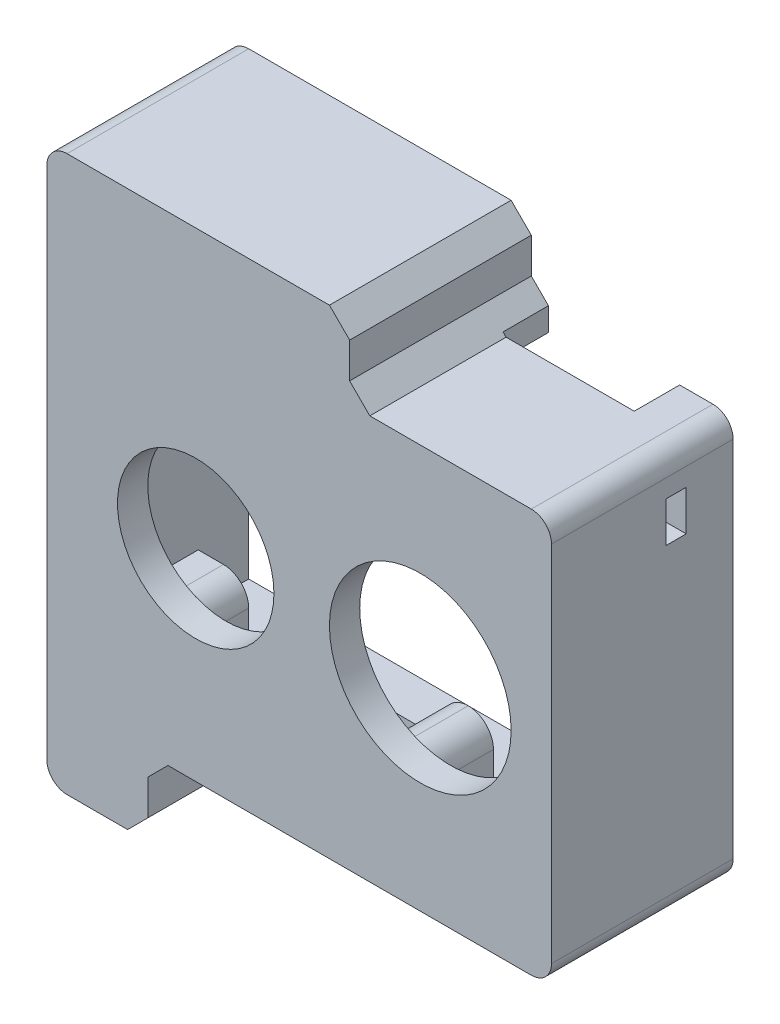
SolidWorks part; units mm, degrees
ref_plane "Front Plane" through (0, 0, 0) normal (0, 0, 1) x (1, 0, 0)
ref_plane "Top Plane" through (0, 0, 0) normal (0, 1, 0) x (1, 0, 0)
ref_plane "Right Plane" through (0, 0, 0) normal (1, 0, 0) x (0, 0, -1)
sketch "Sketch1" plane through (0, 0, 0) normal (0, 0, 1) x (1, 0, 0)
  line L0 (-15, -27.5) -> (-15, -20)
  line L1 (-25, -27.5) -> (-15, -27.5)
  line L2 (-25, -27.5) -> (-25, 27.5)
  line L3 (-25, 27.5) -> (5, 27.5)
  line L4 (25, -20) -> (25, 20)
  line L5 (0, 0) -> (25, 0) construction
  line L6 (0, 0) -> (-25, 0) construction
  line L7 (-23, -18) -> (23, -18)
  line L8 (-23, -18) -> (-23, 18)
  line L9 (-23, 18) -> (23, 18)
  line L10 (23, -18) -> (23, 18)
  line L11 (-23, -18) -> (23, 18) construction
  line L12 (-23, 18) -> (23, -18) construction
  line L13 (-15, -20) -> (25, -20)
  line L14 (5, 27.5) -> (5, 20)
  line L15 (5, 20) -> (25, 20)
  point P0 (0, 0)
  point P1 (-25, 0)
  point P4 (25, 0)
  point P6 (0, 0)
  point P18 (23, 0)
  point P20 (0, 18)
  dimension "D1" = 55
  dimension "D2" = 30
  dimension "D3" = 46
  dimension "D4" = 36
  dimension "D5" = 40
  dimension "D6" = 10
  dimension "D7" = 50
extrude "Boss-Extrude1" add sketch "Sketch1" along normal blind 15
sketch "Sketch2" plane through (0, 0, 15) normal (0, 0, 1) x (1, 0, 0)
  line L12 (-25, 27.5) -> (-25, -27.5)
  line L13 (-25, -27.5) -> (-15, -27.5)
  line L14 (-15, -27.5) -> (-15, -20)
  line L15 (-15, -20) -> (25, -20)
  line L16 (25, -20) -> (25, 20)
  line L17 (25, 20) -> (5, 20)
  line L18 (5, 20) -> (5, 27.5)
  line L19 (5, 27.5) -> (-25, 27.5)
  line L20 (-25, 27.5) -> (-25, -27.5)
  line L21 (-25, -27.5) -> (-15, -27.5)
  line L22 (-15, -27.5) -> (-15, -20)
  line L23 (-15, -20) -> (25, -20)
  line L24 (25, -20) -> (25, 20)
  line L25 (25, 20) -> (5, 20)
  line L26 (5, 20) -> (5, 27.5)
  line L27 (5, 27.5) -> (-25, 27.5)
  dimension "D1" = 0
extrude "Boss-Extrude2" add sketch "Sketch2" along normal blind 3
sketch "Sketch3" plane through (0, 0, 18) normal (0, 0, 1) x (1, 0, 0)
  circle A0 centre (-10.25, 0) radius 7.75
  circle A1 centre (12, 0) radius 9
  point P6 (0, 0)
  point P8 (0, 0)
  point P9 (0, 0)
  point P10 (0, 0)
  dimension "D1" = 18
  dimension "D2" = 15.5
  dimension "D3" = 10.25
  dimension "D4" = 12
extrude "Cut-Extrude1" cut sketch "Sketch3" against normal blind 10
sketch "Sketch4" plane through (0, 0, 15) normal (0, 0, -1) x (-1, 0, 0)
  line L0 (18, -18) -> (18, -13)
  line L1 (23, -18) -> (-23, -18) construction
  line L2 (18, -13) -> (23, -13)
  line L3 (23, 18) -> (23, -18) construction
  line L4 (23, -18) -> (23, -13)
  line L5 (23, -18) -> (18, -18)
  line L6 (-23, 18) -> (23, 18) construction
  line L7 (-1.248, -18) -> (-6.248, -18)
  line L8 (-1.248, -18) -> (-1.248, -13)
  line L9 (-1.248, -13) -> (-6.248, -13)
  line L10 (-6.248, -18) -> (-6.248, -13)
  line L11 (-1.248, 18) -> (-6.248, 18)
  line L12 (-1.248, 18) -> (-1.248, 13)
  line L13 (-1.248, 13) -> (-6.248, 13)
  line L14 (-6.248, 18) -> (-6.248, 13)
  line L16 (18, 18) -> (23, 18)
  line L17 (18, 18) -> (18, 13)
  line L18 (18, 13) -> (23, 13)
  line L19 (23, 18) -> (23, 13)
  circle A0 centre (20.252, -15.1962) radius 1
  circle A1 centre (-3.748, -15.1962) radius 1
  circle A2 centre (-3.748, 15.2038) radius 1
  circle A3 centre (20.252, 15.2038) radius 1
  point P32 (0, 0)
  point P33 (0, 0)
  point P34 (0, 0)
  point P35 (0, 0)
  point P36 (-3.748, -18)
  point P37 (0, 0)
  dimension "D1" = 2
  dimension "D2" = 5
  dimension "D4" = 24
  dimension "D5" = 30.4
extrude "Boss-Extrude3" add sketch "Sketch4" along normal blind 10
fillet "Fillet1" radius 2.5 6 edges at (6.248, -13, 10) (1.248, -13, 10) (-18, -13, 10) (-18, 13, 10) (1.248, 13, 10) (6.248, 13, 10)
sketch "Sketch6" plane through (0, 0, -3) normal (0, 0, -1) x (-1, 0, 0)
  line L0 (20, 22.5) -> (20, -22.5) construction
  circle A0 centre (0, 22.5) radius 1
  circle A1 centre (20, 22.5) radius 1
  circle A2 centre (20, -22.5) radius 1
  dimension "D3" = 2
  dimension "D1" = 22.5
  dimension "D2" = 20
  dimension "D4" = 45
extrude "Cut-Extrude2" cut sketch "Sketch6" against normal blind 10
chamfer "Chamfer1" distance 2 angle 45 4 edges at (-15, -27.5, 9) (5, 27.5, 9) (-15, -20, 9) (5, 20, 9)
fillet "Fillet2" radius 2 4 edges at (-25, 27.5, 9) (-25, -27.5, 9) (25, 20, 9) (25, -20, 9)
sketch "Sketch7" plane through (0, 18, 0) normal (0, -1, 0) x (1, 0, 0)
  line L0 (23, 0) -> (-23, 0) construction
  line L1 (6.7, 0) -> (19.7, 0)
  line L2 (6.7, 0) -> (6.7, 4.5)
  line L3 (6.7, 4.5) -> (19.7, 4.5)
  line L4 (19.7, 0) -> (19.7, 4.5)
  point P6 (13.2, 0)
  dimension "D1" = 13
  dimension "D2" = 4.5
  dimension "D3" = 13.2
extrude "Cut-Extrude3" cut sketch "Sketch7" against normal blind 10
sketch "Sketch8" plane through (0, -18, 0) normal (0, 1, 0) x (1, 0, 0)
  line L0 (-23, 0) -> (23, 0) construction
  line L1 (22.2, 0) -> (9.2, 0)
  line L2 (22.2, 0) -> (22.2, -9.5)
  line L3 (22.2, -9.5) -> (11.7, -9.5)
  line L4 (9.2, 0) -> (9.2, -4.5)
  line L5 (11.7, -9.5) -> (11.7, -4.5)
  line L6 (11.7, -4.5) -> (9.2, -4.5)
  line L8 (0.7, -4.2) -> (-8.3, -4.2)
  line L9 (0.7, -4.2) -> (0.7, -8.2)
  line L10 (0.7, -8.2) -> (-8.3, -8.2)
  line L11 (-8.3, -4.2) -> (-8.3, -8.2)
  point P6 (15.7, 0)
  point P14 (-3.8, -4.2)
  dimension "D1" = 13
  dimension "D2" = 15.7
  dimension "D3" = 9.5
  dimension "D4" = 10.5
  dimension "D5" = 4.5
  dimension "D6" = 3.8
  dimension "D7" = 9
  dimension "D8" = 4.2
  dimension "D9" = 4
extrude "Cut-Extrude4" cut sketch "Sketch8" against normal blind 10
sketch "Sketch9" plane through (23, 0, 0) normal (-1, 0, 0) x (0, 0, 1)
  line L1 (4.65, 12.2) -> (6.65, 12.2)
  line L2 (4.65, 12.2) -> (4.65, 16.2)
  line L3 (4.65, 16.2) -> (6.65, 16.2)
  line L4 (6.65, 12.2) -> (6.65, 16.2)
  point P4 (4.65, 14.2)
  dimension "D1" = 2
  dimension "D2" = 4.65
  dimension "D3" = 14.2
  dimension "D4" = 4
extrude "Cut-Extrude5" cut sketch "Sketch9" against normal blind 10
